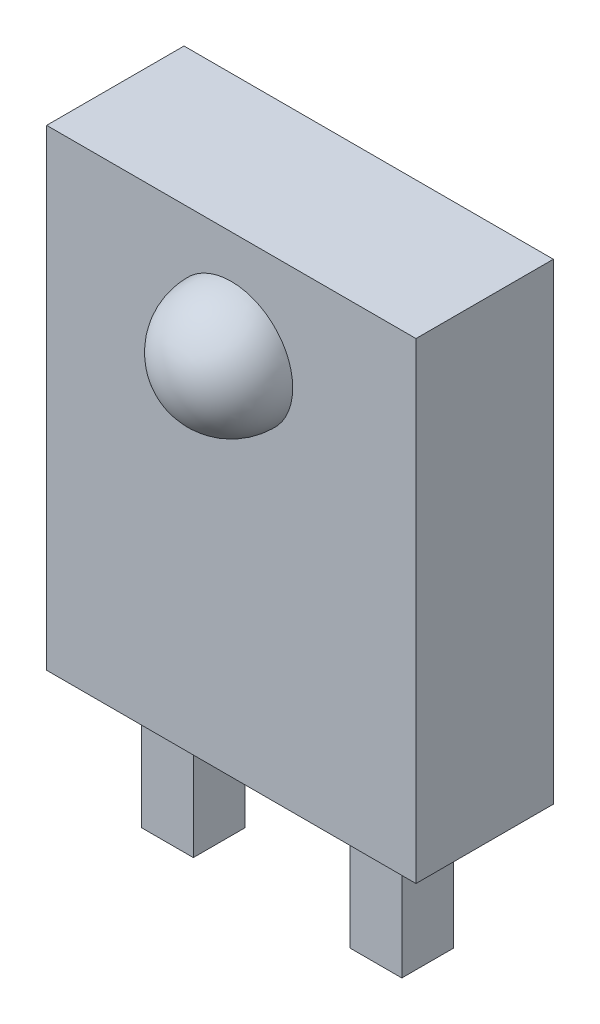
SolidWorks part; units mm, degrees
ref_plane "Front Plane" through (0, 0, 0) normal (0, 0, 1) x (1, 0, 0)
ref_plane "Top Plane" through (0, 0, 0) normal (0, 1, 0) x (1, 0, 0)
ref_plane "Right Plane" through (0, 0, 0) normal (1, 0, 0) x (0, 0, -1)
sketch "Sketch2" plane through (0, 0, 0) normal (0, 0, 1) x (1, 0, 0)
  line L0 (-2.285, -2.92) -> (2.285, -2.92)
  line L1 (-2.285, -2.92) -> (-2.285, 2.92)
  line L2 (2.285, -2.92) -> (2.285, 2.92)
  line L3 (-2.285, 2.92) -> (2.285, 2.92)
  line L4 (-2.285, -2.92) -> (2.285, 2.92) construction
  line L5 (2.285, -2.92) -> (-2.285, 2.92) construction
  point P1 (0, 0)
  dimension "D1" = 5.84
  dimension "D2" = 4.57
extrude "Boss-Extrude1" add sketch "Sketch2" against normal blind 0.56 and the other way blind 1.14
sketch "Sketch3" plane through (0, 0, 1.14) normal (0, 0, 1) x (1, 0, 0)
  line L1 (2.285, 2.92) -> (-2.285, 2.92) construction
  circle A0 centre (0, 1.63) radius 0.76
  dimension "D1" = 1.52
  dimension "D2" = 1.29
extrude "Boss-Extrude2" add sketch "Sketch3" along normal blind 0.76
fillet "Fillet1" radius 0.76 1 edges at (0.76, 1.63, 1.9)
sketch "Sketch4" plane through (0, -2.92, 0) normal (0, -1, 0) x (1, 0, 0)
  line L0 (0.97, 0) -> (1.61, 0)
  line L1 (0.97, 0) -> (0.97, 0.64)
  line L2 (1.61, 0) -> (1.61, 0.64)
  line L3 (0.97, 0.64) -> (1.61, 0.64)
  dimension "D1" = 0.64
  dimension "D2" = 0.64
  dimension "D3" = 0.97
extrude "Boss-Extrude3" add sketch "Sketch4" along normal blind 1.6
sketch "Sketch5" plane through (0, -2.92, 0) normal (0, -1, 0) x (1, 0, 0)
  line L0 (-0.97, 0) -> (-1.61, 0)
  line L1 (-0.97, 0) -> (-0.97, 0.64)
  line L2 (-1.61, 0) -> (-1.61, 0.64)
  line L3 (-0.97, 0.64) -> (-1.61, 0.64)
  dimension "D1" = 0.64
  dimension "D2" = 0.64
  dimension "D3" = 0.97
extrude "Boss-Extrude4" add sketch "Sketch5" along normal blind 1.6
sketch "Sketch6" plane through (0, 2.92, 0) normal (0, 1, 0) x (-1, 0, 0)
  line L0 (0, 1.14) -> (0, 3.8369) construction
  line L1 (-2.285, 1.14) -> (2.285, 1.14) construction
  line L2 (0, 1.14) -> (-63.4415, 30.7233)
  line L3 (0, 1.14) -> (63.4415, 30.7233)
  dimension "D1" = 65
  dimension "D2" = 65
  dimension "D3" = 70
  dimension "D4" = 70
